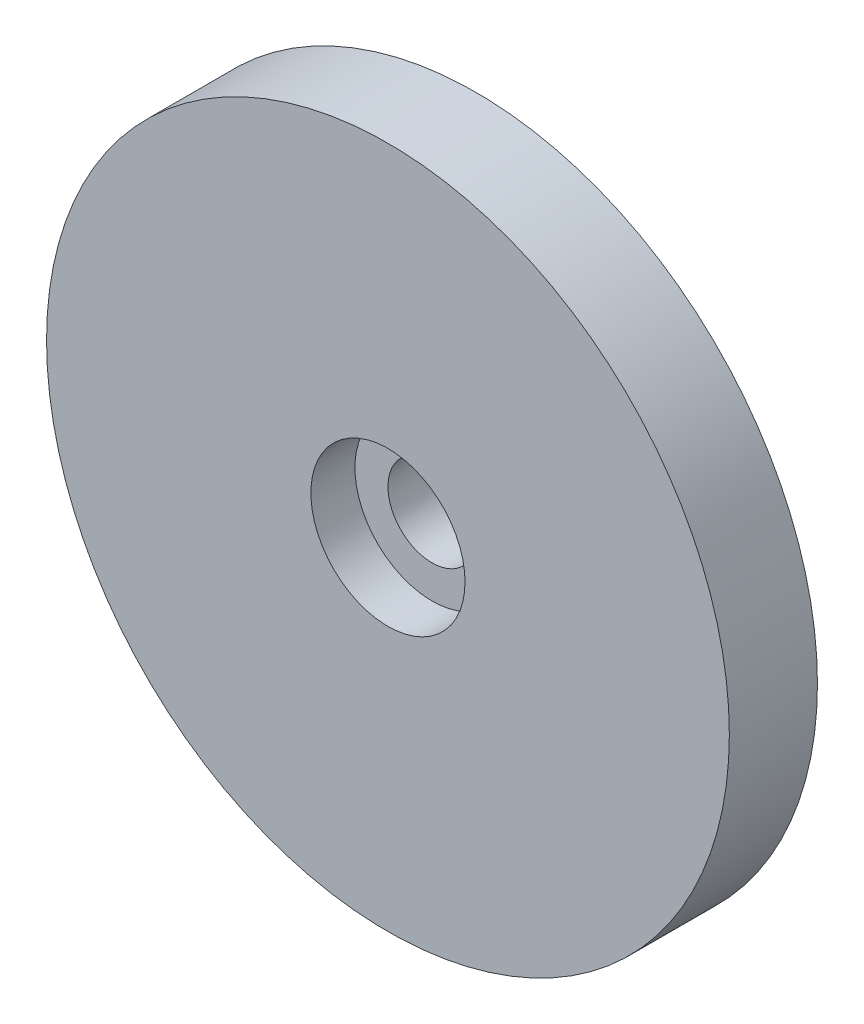
SolidWorks part; units mm, degrees
ref_plane "前视基准面" through (0, 0, 0) normal (0, 0, 1) x (1, 0, 0)
ref_plane "上视基准面" through (0, 0, 0) normal (0, 1, 0) x (1, 0, 0)
ref_plane "右视基准面" through (0, 0, 0) normal (1, 0, 0) x (0, 0, -1)
other "Configuration Table"
sketch "草图1" plane through (0, 0, 0) normal (0, 0, 1) x (1, 0, 0)
  circle A1 centre (0, 0) radius 7.75
  dimension "D1" = 15.5
extrude "凸台-拉伸1" add sketch "草图1" along normal blind 2
sketch "草图2" plane through (0, 0, 2) normal (0, 0, 1) x (1, 0, 0)
  circle A0 centre (0, 0) radius 1.75
  circle A1 centre (0, 0) radius 1
  dimension "D1" = 3.5
  dimension "D2" = 2
extrude "切除-拉伸1" cut sketch "草图2" against normal through all contours A1
extrude "切除-拉伸2" cut sketch "草图2<3>" against normal blind 1
sketch "草图2<3>" plane through (0, 0, 2) normal (0, 0, 1) x (1, 0, 0) same geometry as "草图2"
